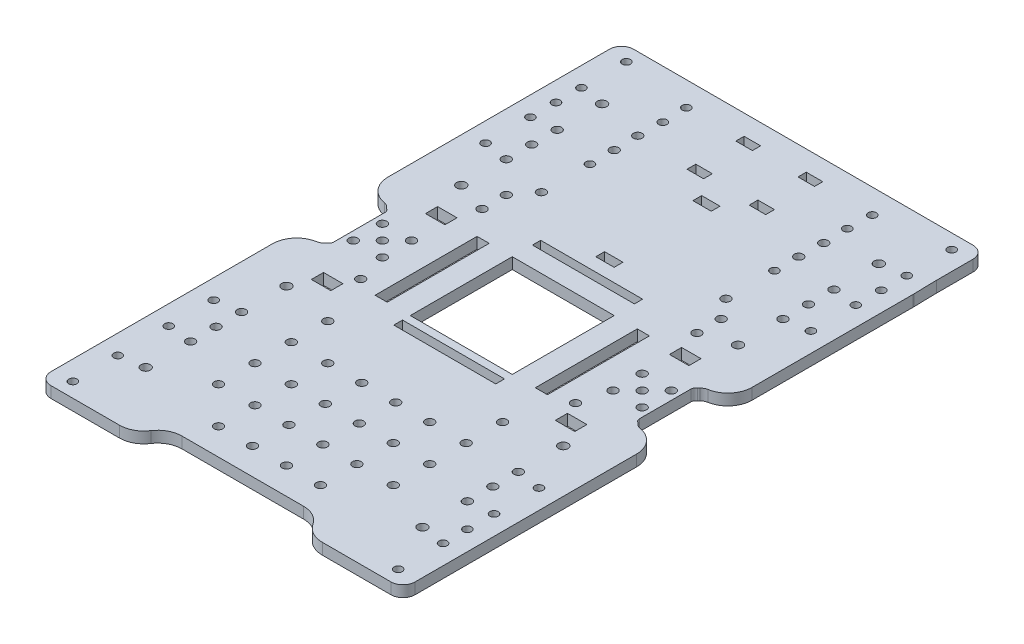
SolidWorks part; units mm, degrees
ref_plane "前视基准面" through (0, 0, 0) normal (0, 0, 1) x (1, 0, 0)
ref_plane "上视基准面" through (0, 0, 0) normal (0, 1, 0) x (1, 0, 0)
ref_plane "右视基准面" through (0, 0, 0) normal (1, 0, 0) x (0, 0, -1)
other "Configuration Table"
sketch "草图2" plane through (0, 0, 0) normal (0, 1, 0) x (1, 0, 0)
  line L0 (-65, 0) -> (65, 0) construction
  line L1 (-65, 100) -> (65, 100)
  line L2 (-65, 100) -> (-65, -100)
  line L3 (-65, -100) -> (65, -100)
  line L4 (65, 100) -> (65, -100)
  line L5 (-65, 100) -> (65, -100) construction
  line L6 (-65, -100) -> (65, 100) construction
  line L7 (65, 0) -> (63, 0) construction
  line L8 (63, 0) -> (59.5, 0) construction
  line L9 (59.5, 0) -> (47.5, 0) construction
  line L10 (47.5, 0) -> (53.5, 0) construction
  line L11 (53.5, 0) -> (53.5, 6) construction
  line L12 (53.5, 6) -> (53.5, -6) construction
  line L13 (53.5, -6) -> (47.5, -6) construction
  line L14 (47.5, -6) -> (47.5, 6) construction
  line L15 (47.5, 6) -> (59.5, 6) construction
  line L16 (59.5, 6) -> (59.5, -6) construction
  line L17 (-65, 0) -> (-63, 0) construction
  line L18 (-63, 0) -> (-59.5, 0) construction
  line L19 (-59.5, 0) -> (-47.5, 0) construction
  line L20 (-47.5, 0) -> (-53.5, 0) construction
  line L21 (-53.5, 0) -> (-53.5, 6) construction
  line L22 (-53.5, 6) -> (-53.5, -6) construction
  line L23 (-53.5, -6) -> (-59.5, -6) construction
  line L24 (-59.5, -6) -> (-59.5, 6) construction
  line L25 (-59.5, 6) -> (-47.5, 6) construction
  line L26 (-47.5, 6) -> (-47.5, -6) construction
  circle A0 centre (-59.5, 6) radius 1.8
  circle A1 centre (-47.5, 6) radius 1.8
  circle A2 centre (-59.5, -6) radius 1.8
  circle A3 centre (-47.5, -6) radius 1.8
  circle A4 centre (-53.5, 0) radius 1.8
  circle A5 centre (53.5, 0) radius 1.8
  circle A6 centre (59.5, 6) radius 1.8
  circle A7 centre (59.5, -6) radius 1.8
  circle A8 centre (47.5, -6) radius 1.8
  circle A9 centre (47.5, 6) radius 1.8
  point P0 (0, 0)
  dimension "D13" = 3.6
  dimension "D14" = 3.6
  dimension "D15" = 3.6
  dimension "D16" = 3.6
  dimension "D17" = 3.6
  dimension "D18" = 3.6
  dimension "D19" = 3.6
  dimension "D20" = 3.6
  dimension "D21" = 3.6
  dimension "D22" = 3.6
  dimension "D1" = 200
  dimension "D2" = 130
  dimension "D3" = 2
  dimension "D4" = 3.5
  dimension "D5" = 12
  dimension "D6" = 6
  dimension "D7" = 12
  dimension "D8" = 2
  dimension "D9" = 3.5
  dimension "D10" = 12
  dimension "D11" = 6
  dimension "D12" = 12
extrude "凸台-拉伸1" add sketch "草图2" along normal blind 4.6
fillet "圆角1" radius 5 4 edges at (-65, 2.3, -100) (65, 2.3, -100) (-65, 2.3, 100) (65, 2.3, 100)
sketch "草图3" plane through (0, 4.6, 0) normal (0, 1, 0) x (1, 0, 0)
  line L0 (-65, 0) -> (65, 0) construction
  line L1 (-65, 95) -> (-65, -95) construction
  line L2 (65, -95) -> (65, 95) construction
  line L4 (-63, 12) -> (-67, 12)
  line L5 (-63, 12) -> (-63, -12)
  line L6 (-63, -12) -> (-67, -12)
  line L7 (-67, 12) -> (-67, -12)
  line L8 (-63, 12) -> (-67, -12) construction
  line L9 (-63, -12) -> (-67, 12) construction
  line L10 (63, 12) -> (67, 12)
  line L11 (63, 12) -> (63, -12)
  line L12 (63, -12) -> (67, -12)
  line L13 (67, 12) -> (67, -12)
  line L14 (63, 12) -> (67, -12) construction
  line L15 (63, -12) -> (67, 12) construction
  dimension "D1" = 24
  dimension "D2" = 4
  dimension "D3" = 24
  dimension "D4" = 4
extrude "切除-拉伸1" cut sketch "草图3" against normal blind 4.6
fillet "圆角2" radius 2 4 edges at (65, 2.3, 12) (65, 2.3, -12) (-65, 2.3, 12) (-65, 2.3, -12)
fillet "圆角3" radius 2 4 edges at (-63, 2.3, 12) (-63, 2.3, -12) (63, 2.3, 12) (63, 2.3, -12)
sketch "草图4" plane through (0, 0, 0) normal (0, 1, 0) x (1, 0, 0)
  line L0 (65, 14) -> (57, 14) construction
  line L1 (57, 14) -> (57, 120) construction
  line L2 (65, -14) -> (57, -14) construction
  line L3 (65, -95) -> (65, -14) construction
  line L4 (57, -14) -> (57, -94) construction
  line L5 (57, -94) -> (57, -65) construction
  line L6 (57, -65) -> (57, -54) construction
  line L7 (-65, -94) -> (-57, -94) construction
  line L8 (-65, -14) -> (-65, -95) construction
  line L9 (-57, -94) -> (-57, -65) construction
  line L10 (-57, -65) -> (-57, -54.5) construction
  line L11 (-57, -54.5) -> (-57, -65) construction
  line L12 (-57, -65) -> (-57, -36) construction
  line L13 (57, -65) -> (57, -36) construction
  line L14 (57, 14) -> (57, 36) construction
  line L15 (57, 36) -> (57, 65) construction
  line L16 (57, 65) -> (57, 75.5) construction
  line L17 (57, 75.5) -> (57, 54.5) construction
  line L18 (57, 65) -> (57, 94) construction
  line L19 (-65, 14) -> (-57, 14) construction
  line L20 (-57, 14) -> (-57, 36) construction
  line L21 (-57, 36) -> (-57, 54.5) construction
  line L22 (-57, 54.5) -> (-57, 65) construction
  line L23 (-57, 65) -> (-57, 75.5) construction
  line L24 (-57, 75.5) -> (-57, 94) construction
  line L25 (-57, -65) -> (-57, -75.5) construction
  line L26 (-57, -75.5) -> (57, -75.5) construction
  line L27 (57, -65) -> (57, -54.5) construction
  arc A0 (65, -14) -> (64, -12.2679) centre (63, -14) ccw construction
  circle A1 centre (57, 65) radius 1.8
  circle A2 centre (57, 75.5) radius 1.8
  circle A3 centre (57, 54.5) radius 1.8
  circle A4 centre (57, 94) radius 1.95
  circle A5 centre (57, 36) radius 1.95
  circle A6 centre (-57, 94) radius 1.95
  circle A7 centre (-57, 75.5) radius 1.8
  circle A8 centre (-57, 65) radius 1.8
  circle A9 centre (-57, 54.5) radius 1.8
  circle A10 centre (-57, 36) radius 1.95
  circle A11 centre (-57, -36) radius 1.95
  circle A12 centre (-57, -65) radius 1.8
  circle A13 centre (-57, -54.5) radius 1.8
  circle A14 centre (-57, -75.5) radius 1.8
  circle A15 centre (-57, -94) radius 1.95
  circle A16 centre (57, -65) radius 1.8
  circle A18 centre (57, -75.5) radius 1.8
  circle A19 centre (57, -54.5) radius 1.8
  circle A20 centre (57, -36) radius 1.95
  circle A21 centre (57, -94) radius 1.95
  dimension "D15" = 3.6
  dimension "D16" = 3.6
  dimension "D17" = 3.6
  dimension "D18" = 3.9
  dimension "D19" = 3.9
  dimension "D20" = 3.9
  dimension "D21" = 3.6
  dimension "D22" = 3.6
  dimension "D23" = 3.6
  dimension "D24" = 3.9
  dimension "D25" = 3.9
  dimension "D26" = 3.6
  dimension "D27" = 3.6
  dimension "D29" = 3.6
  dimension "D30" = 3.9
  dimension "D31" = 3.6
  dimension "D32" = 10.5
  dimension "D33" = 3.6
  dimension "D34" = 3.6
  dimension "D35" = 3.9
  dimension "D36" = 3.9
  dimension "D1" = 8
  dimension "D2" = 106
  dimension "D3" = 8
  dimension "D4" = 80
  dimension "D5" = 29
  dimension "D6" = 11
  dimension "D7" = 8
  dimension "D8" = 29
  dimension "D9" = 22
  dimension "D10" = 29
  dimension "D11" = 10.5
  dimension "D12" = 21
  dimension "D13" = 29
  dimension "D14" = 8
  dimension "D28" = 10.5
extrude "切除-拉伸2" cut sketch "草图4" along normal blind 4.6
sketch "草图5" plane through (0, 4.6, 0) normal (0, 1, 0) x (1, 0, 0)
  line L0 (0, 100) -> (38.3, 100) construction
  line L1 (60, 100) -> (-60, 100) construction
  line L2 (38.3, 100) -> (-38.3, 100) construction
  line L3 (-38.3, 100) -> (-38.3, 90) construction
  line L4 (-38.3, 90) -> (-12.8, 90) construction
  line L5 (38.3, 100) -> (38.3, 90) construction
  line L6 (38.3, 90) -> (12.8, 90) construction
  line L7 (0, 21) -> (0, 31) construction
  line L8 (-16.2, 91.8) -> (-9.4, 91.8)
  line L9 (-16.2, 91.8) -> (-16.2, 88.2)
  line L10 (-16.2, 88.2) -> (-9.4, 88.2)
  line L11 (-9.4, 91.8) -> (-9.4, 88.2)
  line L12 (-16.2, 91.8) -> (-9.4, 88.2) construction
  line L13 (-16.2, 88.2) -> (-9.4, 91.8) construction
  line L14 (9.4, 91.8) -> (16.2, 91.8)
  line L15 (9.4, 91.8) -> (9.4, 88.2)
  line L16 (9.4, 88.2) -> (16.2, 88.2)
  line L17 (16.2, 91.8) -> (16.2, 88.2)
  line L18 (9.4, 91.8) -> (16.2, 88.2) construction
  line L19 (9.4, 88.2) -> (16.2, 91.8) construction
  line L20 (-21, 21) -> (21, 21)
  line L21 (-21, 21) -> (-21, -21)
  line L22 (-21, -21) -> (21, -21)
  line L23 (21, 21) -> (21, -21)
  line L24 (-21, 21) -> (21, -21) construction
  line L25 (-21, -21) -> (21, 21) construction
  line L26 (0, 31) -> (0, -21) construction
  line L27 (0, -21) -> (0, -31) construction
  line L28 (-60, -100) -> (60, -100) construction
  line L29 (-21, 32.7) -> (21, 32.7)
  line L30 (-21, 32.7) -> (-21, 29.3)
  line L31 (-21, 29.3) -> (21, 29.3)
  line L32 (21, 32.7) -> (21, 29.3)
  line L33 (-21, 32.7) -> (21, 29.3) construction
  line L34 (-21, 29.3) -> (21, 32.7) construction
  line L35 (-21, -29.3) -> (21, -29.3)
  line L36 (-21, -29.3) -> (-21, -32.7)
  line L37 (-21, -32.7) -> (21, -32.7)
  line L38 (21, -29.3) -> (21, -32.7)
  line L39 (-21, -29.3) -> (21, -32.7) construction
  line L40 (-21, -32.7) -> (21, -29.3) construction
  line L41 (-35, -91) -> (35, -91)
  line L42 (-35, -91) -> (-35, -109)
  line L43 (-35, -109) -> (35, -109)
  line L44 (35, -91) -> (35, -109)
  line L45 (-35, -91) -> (35, -109) construction
  line L46 (-35, -109) -> (35, -91) construction
  circle A0 centre (38.3, 90) radius 1.8
  circle A1 centre (-38.3, 90) radius 1.8
  point P19 (0, 0)
  point P37 (0, -100)
  dimension "D7" = 3.6
  dimension "D8" = 3.6
  dimension "D1" = 38.3
  dimension "D2" = 76.6
  dimension "D3" = 10
  dimension "D4" = 25.5
  dimension "D5" = 10
  dimension "D6" = 25.5
  dimension "D9" = 3.6
  dimension "D10" = 6.8
  dimension "D11" = 3.6
  dimension "D12" = 6.8
  dimension "D13" = 42
  dimension "D14" = 10
  dimension "D15" = 10
  dimension "D16" = 3.4
  dimension "D17" = 42
  dimension "D18" = 3.4
  dimension "D19" = 42
  dimension "D20" = 18
  dimension "D21" = 70
extrude "切除-拉伸3" cut sketch "草图5" against normal blind 4.6
fillet "圆角4" radius 10 2 edges at (-35, 2.3, 100) (35, 2.3, 100)
fillet "圆角5" radius 10 2 edges at (-35, 2.3, 91) (35, 2.3, 91)
sketch "草图6" plane through (0, 4.6, 0) normal (0, 1, 0) x (1, 0, 0)
  line L0 (0, -91) -> (0, -85) construction
  line L1 (28.2466, -91) -> (-28.2466, -91) construction
  line L2 (0, -85) -> (-7, -85) construction
  line L3 (-7, -85) -> (7, -85) construction
  line L4 (7, -85) -> (21, -85) construction
  line L5 (21, -85) -> (21, -70) construction
  line L6 (21, -70) -> (21, -55) construction
  line L7 (21, -55) -> (7, -55) construction
  line L8 (7, -55) -> (-7, -55) construction
  line L9 (-7, -55) -> (-21, -55) construction
  line L10 (-21, -55) -> (-35, -55) construction
  line L11 (-35, -55) -> (-35, -70) construction
  line L12 (-35, -70) -> (-35, -85) construction
  line L13 (-35, -85) -> (-21, -85) construction
  line L14 (21, -85) -> (35, -85) construction
  line L15 (35, -85) -> (35, -70) construction
  line L16 (35, -70) -> (35, -55) construction
  line L17 (35, -55) -> (35, -40) construction
  line L18 (35, -40) -> (21, -40) construction
  line L19 (21, -40) -> (7, -40) construction
  line L20 (7, -40) -> (-7, -40) construction
  line L21 (-7, -40) -> (-21, -40) construction
  line L22 (-21, -40) -> (-35, -40) construction
  line L23 (-35, -40) -> (-35, -70) construction
  line L24 (-35, -70) -> (-21, -70) construction
  line L25 (-21, -70) -> (-7, -70) construction
  line L26 (-7, -70) -> (7, -70) construction
  line L27 (21, -70) -> (36, -70) construction
  line L28 (36, -70) -> (36, -55) construction
  line L29 (36, -55) -> (36, -40) construction
  line L30 (-21, -70) -> (-36, -70) construction
  line L31 (-36, -70) -> (-36, -55) construction
  line L32 (-36, -55) -> (-36, -40) construction
  circle A0 centre (-7, -85) radius 1.8
  circle A1 centre (-21, -85) radius 1.8
  circle A2 centre (7, -85) radius 1.8
  circle A3 centre (21, -85) radius 1.8
  circle A4 centre (21, -70) radius 1.8
  circle A5 centre (7, -70) radius 1.8
  circle A6 centre (-7, -70) radius 1.8
  circle A7 centre (-21, -70) radius 1.8
  circle A8 centre (-21, -55) radius 1.8
  circle A9 centre (-7, -55) radius 1.8
  circle A10 centre (7, -55) radius 1.8
  circle A11 centre (21, -55) radius 1.8
  circle A12 centre (36, -70) radius 1.8
  circle A13 centre (36, -55) radius 1.8
  circle A14 centre (36, -40) radius 1.8
  circle A15 centre (-36, -40) radius 1.8
  circle A16 centre (-36, -55) radius 1.8
  circle A17 centre (-36, -70) radius 1.8
  dimension "D15" = 3.6
  dimension "D16" = 3.6
  dimension "D17" = 3.6
  dimension "D18" = 3.6
  dimension "D19" = 3.6
  dimension "D20" = 3.6
  dimension "D21" = 3.6
  dimension "D22" = 3.6
  dimension "D23" = 3.6
  dimension "D24" = 3.6
  dimension "D25" = 3.6
  dimension "D26" = 3.6
  dimension "D27" = 15
  dimension "D33" = 3.6
  dimension "D34" = 3.6
  dimension "D35" = 3.6
  dimension "D36" = 3.6
  dimension "D37" = 3.6
  dimension "D38" = 3.6
  dimension "D1" = 6
  dimension "D2" = 7
  dimension "D3" = 14
  dimension "D4" = 14
  dimension "D5" = 15
  dimension "D6" = 15
  dimension "D7" = 14
  dimension "D8" = 14
  dimension "D9" = 14
  dimension "D10" = 14
  dimension "D11" = 15
  dimension "D12" = 14
  dimension "D13" = 14
  dimension "D14" = 15
  dimension "D28" = 15
  dimension "D29" = 15
  dimension "D30" = 15
  dimension "D31" = 15
  dimension "D32" = 15
extrude "切除-拉伸4" cut sketch "草图6" against normal blind 4.6
sketch "草图7" plane through (0, 4.6, 0) normal (0, 1, 0) x (1, 0, 0)
  line L0 (0, 100) -> (38, 100) construction
  line L1 (60, 100) -> (-60, 100) construction
  line L2 (38, 100) -> (-38, 100) construction
  line L3 (-38, 100) -> (-38, 80) construction
  line L4 (-38, 80) -> (-38, 50) construction
  line L5 (-38, 50) -> (38, 50) construction
  line L6 (38, 50) -> (38, 80) construction
  circle A0 centre (-38, 80) radius 1.8
  circle A1 centre (38, 80) radius 1.8
  circle A2 centre (38, 50) radius 1.8
  circle A3 centre (-38, 50) radius 1.8
  dimension "D7" = 3.6
  dimension "D8" = 3.6
  dimension "D9" = 3.6
  dimension "D10" = 3.6
  dimension "D1" = 38
  dimension "D2" = 76
  dimension "D3" = 20
  dimension "D4" = 30
  dimension "D5" = 76
  dimension "D6" = 30
extrude "切除-拉伸5" cut sketch "草图7" against normal blind 4.6
sketch "草图8" plane through (0, 4.6, 0) normal (0, 1, 0) x (1, 0, 0)
  line L0 (-38, 80) -> (38, 50) construction
  line L1 (38, 50) -> (0, 65) construction
  line L2 (0, 65) -> (-35, 65) construction
  line L3 (-35, 65) -> (35, 65) construction
  line L4 (35, 65) -> (0, 65) construction
  line L5 (0, 65) -> (0, 80) construction
  line L6 (0, 80) -> (0, 40) construction
  line L8 (-3.7805, 81.7985) -> (3.7805, 81.7985)
  line L9 (-3.7805, 81.7985) -> (-3.7805, 78.2015)
  line L10 (-3.7805, 78.2015) -> (3.7805, 78.2015)
  line L11 (3.7805, 81.7985) -> (3.7805, 78.2015)
  line L12 (-3.7805, 81.7985) -> (3.7805, 78.2015) construction
  line L13 (-3.7805, 78.2015) -> (3.7805, 81.7985) construction
  line L14 (-3.7805, 38.1892) -> (3.7805, 38.1892)
  line L15 (-3.7805, 38.1892) -> (-3.7805, 41.8108)
  line L16 (-3.7805, 41.8108) -> (3.7805, 41.8108)
  line L17 (3.7805, 38.1892) -> (3.7805, 41.8108)
  line L18 (-3.7805, 38.1892) -> (3.7805, 41.8108) construction
  line L19 (-3.7805, 41.8108) -> (3.7805, 38.1892) construction
  line L20 (33.2, 68.4) -> (36.8, 68.4)
  line L21 (33.2, 68.4) -> (33.2, 61.6)
  line L22 (33.2, 61.6) -> (36.8, 61.6)
  line L23 (36.8, 68.4) -> (36.8, 61.6)
  line L24 (33.2, 68.4) -> (36.8, 61.6) construction
  line L25 (33.2, 61.6) -> (36.8, 68.4) construction
  line L26 (-36.8, 68.4) -> (-33.2, 68.4)
  line L27 (-36.8, 68.4) -> (-36.8, 61.6)
  line L28 (-36.8, 61.6) -> (-33.2, 61.6)
  line L29 (-33.2, 68.4) -> (-33.2, 61.6)
  line L30 (-36.8, 68.4) -> (-33.2, 61.6) construction
  line L31 (-36.8, 61.6) -> (-33.2, 68.4) construction
  dimension "D1" = 35
  dimension "D2" = 70
  dimension "D3" = 40
  dimension "D4" = 6.8
  dimension "D5" = 3.6
  dimension "D6" = 6.8
  dimension "D7" = 3.6
extrude "切除-拉伸6" cut sketch "草图8" against normal blind 4.6
sketch "草图10" plane through (0, 4.6, 0) normal (0, 1, 0) x (1, 0, 0)
  line L0 (0, 0) -> (44.25, 0) construction
  line L1 (44.25, 0) -> (-44.25, 0) construction
  line L2 (36, -38.2) -> (73.5514, -38.2) construction
  line L3 (73.5514, -38.2) -> (-76.1567, -38.2) construction
  line L4 (44.25, 0) -> (44.25, -38.2) construction
  line L5 (44.25, -38.2) -> (44.25, -18.2) construction
  line L6 (-44.25, 0) -> (-44.25, -38.2) construction
  line L7 (-44.25, -38.2) -> (-44.25, -18.1899) construction
  line L8 (-44.25, -18.1899) -> (-43.1477, 41.8) construction
  line L9 (-43.1477, 41.8) -> (44.25, 41.8) construction
  line L10 (0, 38.1892) -> (-44.25, 38.1892) construction
  line L11 (-3.7805, 38.1892) -> (3.7805, 38.1892) construction
  line L12 (-44.25, 38.1892) -> (44.25, 38.1892) construction
  line L13 (-44.25, -18.1899) -> (-44.25, 41.8101) construction
  line L14 (44.25, -18.2) -> (44.25, 41.8) construction
  line L15 (44.25, -18.2) -> (44.25, -8.2) construction
  line L16 (-44.25, -18.1899) -> (-44.25, -8.1899) construction
  line L17 (-44.25, -18.1899) -> (-44.25, 31.8101) construction
  line L18 (-44.25, 31.8101) -> (44.25, 31.8101) construction
  circle A0 centre (36, -40) radius 1.8 construction
  circle A1 centre (44.25, 41.8) radius 1.8
  circle A2 centre (-44.25, 41.8101) radius 1.8
  circle A3 centre (-44.25, -18.1899) radius 1.8
  circle A4 centre (44.25, -18.2) radius 1.8
  circle A5 centre (-44.25, 31.8101) radius 1.8
  circle A6 centre (44.25, 31.8101) radius 1.8
  dimension "D9" = 3.6
  dimension "D10" = 3.6
  dimension "D11" = 3.6
  dimension "D12" = 3.6
  dimension "D16" = 3.6
  dimension "D17" = 3.6
  dimension "D1" = 44.25
  dimension "D2" = 88.5
  dimension "D3" = 20
  dimension "D4" = 60
  dimension "D5" = 44.25
  dimension "D6" = 88.5
  dimension "D7" = 60
  dimension "D8" = 60
  dimension "D13" = 10
  dimension "D14" = 10
  dimension "D15" = 50
extrude "切除-拉伸8" cut sketch "草图10" against normal blind 4.6
sketch "草图9" plane through (0, 4.6, 0) normal (0, 1, 0) x (1, 0, 0)
  line L0 (21, 0) -> (33, 0) construction
  line L1 (21, -21) -> (21, 21) construction
  line L2 (-21, 0) -> (-33, 0) construction
  line L3 (-21, 21) -> (-21, -21) construction
  line L4 (35.5, -21) -> (65, -21) construction
  line L9 (30.5, 21) -> (35.5, -21) construction
  line L10 (30.5, -21) -> (35.5, 21) construction
  line L15 (-35.5, 21) -> (-30.5, -21) construction
  line L16 (-35.5, -21) -> (-30.5, 21) construction
  line L17 (65, -95) -> (65, -14) construction
  line L18 (-35.5, -21) -> (-65, -21) construction
  line L23 (46.25, -18.5) -> (54.25, -23.5) construction
  line L24 (46.25, -23.5) -> (54.25, -18.5) construction
  line L25 (-65, -14) -> (-65, -95) construction
  line L26 (-35.5, 21) -> (-65, 21) construction
  line L31 (-54.25, -18.5) -> (-46.25, -23.5) construction
  line L32 (-54.25, -23.5) -> (-46.25, -18.5) construction
  line L33 (-65, 95) -> (-65, 14) construction
  line L34 (35.5, 21) -> (65, 21) construction
  line L35 (-54.25, 23.5) -> (-46.25, 23.5)
  line L36 (-54.25, 23.5) -> (-54.25, 18.5)
  line L37 (-54.25, 18.5) -> (-46.25, 18.5)
  line L38 (-46.25, 23.5) -> (-46.25, 18.5)
  line L39 (-54.25, 23.5) -> (-46.25, 18.5) construction
  line L40 (-54.25, 18.5) -> (-46.25, 23.5) construction
  line L41 (65, 14) -> (65, 95) construction
  line L42 (50.25, -21) -> (50.25, -31) construction
  line L43 (46.25, 23.5) -> (54.25, 23.5)
  line L44 (46.25, 23.5) -> (46.25, 18.5)
  line L45 (46.25, 18.5) -> (54.25, 18.5)
  line L46 (54.25, 23.5) -> (54.25, 18.5)
  line L47 (46.25, 23.5) -> (54.25, 18.5) construction
  line L48 (46.25, 18.5) -> (54.25, 23.5) construction
  line L49 (50.25, -31) -> (50.25, -26) construction
  line L50 (50.25, -26) -> (-50.25, -26) construction
  line L52 (-54.25, -23.5) -> (-46.25, -23.5)
  line L53 (-54.25, -23.5) -> (-54.25, -28.5)
  line L54 (-54.25, -28.5) -> (-46.25, -28.5)
  line L55 (-46.25, -23.5) -> (-46.25, -28.5)
  line L56 (-54.25, -23.5) -> (-46.25, -28.5) construction
  line L57 (-54.25, -28.5) -> (-46.25, -23.5) construction
  line L58 (46.25, -23.5) -> (54.25, -23.5)
  line L59 (46.25, -23.5) -> (46.25, -28.5)
  line L60 (46.25, -28.5) -> (54.25, -28.5)
  line L61 (54.25, -23.5) -> (54.25, -28.5)
  line L62 (46.25, -23.5) -> (54.25, -28.5) construction
  line L63 (46.25, -28.5) -> (54.25, -23.5) construction
  line L64 (30.5, 21) -> (35.5, 21)
  line L65 (30.5, 21) -> (30.5, -21)
  line L66 (30.5, -21) -> (35.5, -21)
  line L67 (35.5, 21) -> (35.5, -21)
  line L68 (30.5, 21) -> (35.5, -21) construction
  line L69 (30.5, -21) -> (35.5, 21) construction
  line L70 (-35.5, 21) -> (-30.5, 21)
  line L71 (-35.5, 21) -> (-35.5, -21)
  line L72 (-35.5, -21) -> (-30.5, -21)
  line L73 (-30.5, 21) -> (-30.5, -21)
  line L74 (-35.5, 21) -> (-30.5, -21) construction
  line L75 (-35.5, -21) -> (-30.5, 21) construction
  point P17 (50.25, -21)
  point P25 (-50.25, -21)
  point P33 (-50.25, 21)
  point P41 (50.25, 21)
  dimension "D1" = 12
  dimension "D2" = 12
  dimension "D3" = 42
  dimension "D4" = 5
  dimension "D5" = 42
  dimension "D6" = 5
  dimension "D7" = 5
  dimension "D8" = 8
  dimension "D9" = 5
  dimension "D10" = 8
  dimension "D11" = 5
  dimension "D12" = 8
  dimension "D13" = 5
  dimension "D14" = 8
  dimension "D15" = 10
  dimension "D16" = 5
  dimension "D17" = 8
  dimension "D18" = 5
  dimension "D19" = 8
extrude "切除-拉伸9" cut sketch "草图9" against normal blind 4.6
sketch "草图12" plane through (0, 0, 0) normal (0, -1, 0) x (1, 0, 0)
  line L0 (-46.25, 28.5) -> (-46.25, 23.5) construction
  line L1 (-65, 100) -> (-46.25, 100)
  line L2 (-65, 100) -> (-65, 28.5)
  line L3 (-65, 28.5) -> (-46.25, 28.5)
  line L4 (-46.25, 100) -> (-46.25, 28.5)
  line L5 (-54.25, 28.5) -> (-46.25, 28.5) construction
  line L6 (65, 95) -> (65, 100.0021) construction
  line L7 (-60, -100) -> (-65, -100) construction
  line L8 (65, 100.0021) -> (46.25, 100.0021)
  line L9 (65, 100.0021) -> (65, 28.5)
  line L10 (65, 28.5) -> (46.25, 28.5)
  line L11 (46.25, 100.0021) -> (46.25, 28.5)
  line L12 (-46.25, -23.5) -> (-54.25, -23.5) construction
  line L13 (-65, -100) -> (-50.25, -100)
  line L14 (-65, -100) -> (-65, -23.5)
  line L15 (-65, -23.5) -> (-50.25, -23.5)
  line L16 (-50.25, -100) -> (-50.25, -23.5)
  line L17 (54.25, -23.5) -> (46.25, -23.5) construction
  line L18 (65, -99.9979) -> (50.25, -99.9979)
  line L19 (65, -99.9979) -> (65, -23.5)
  line L20 (65, -23.5) -> (50.25, -23.5)
  line L21 (50.25, -99.9979) -> (50.25, -23.5)
  line L22 (-50.25, -55.9334) -> (50.25, -55.9334) construction
  line L23 (50.25, -55.9334) -> (50.25, -72.845) construction
  line L24 (50.25, -72.845) -> (-50.25, -72.845) construction
  line L25 (-21, 85) -> (-21, 70) construction
  line L26 (-21, 70) -> (-21, 77.5) construction
  line L27 (-21, 77.5) -> (-46.25, 77.5) construction
  line L28 (-46.25, 77.5) -> (46.25, 77.5) construction
  line L29 (46.25, 77.5) -> (0, 77.5) construction
  line L30 (0, 77.5) -> (0, 62.5) construction
  line L31 (0, 62.5) -> (0, 47.5) construction
  line L32 (0, 77.5) -> (0, 92.5) construction
  line L33 (-28.2466, 91) -> (-46.25, 91) construction
  line L34 (-46.25, 91) -> (46.25, 91) construction
  line L35 (-21, 32.7) -> (-46.25, 32.7) construction
  line L36 (-46.25, 79.5003) -> (46.25, 79.5003)
  line L37 (-46.25, 79.5003) -> (-46.25, 75.4997)
  line L38 (-46.25, 75.4997) -> (46.25, 75.4997)
  line L39 (46.25, 79.5003) -> (46.25, 75.4997)
  line L40 (-46.25, 79.5003) -> (46.25, 75.4997) construction
  line L41 (-46.25, 75.4997) -> (46.25, 79.5003) construction
  line L42 (-46.25, 64.5) -> (46.25, 64.5)
  line L43 (-46.25, 64.5) -> (-46.25, 60.5)
  line L44 (-46.25, 60.5) -> (46.25, 60.5)
  line L45 (46.25, 64.5) -> (46.25, 60.5)
  line L46 (-46.25, 64.5) -> (46.25, 60.5) construction
  line L47 (-46.25, 60.5) -> (46.25, 64.5) construction
  line L48 (-46.25, 49.5) -> (46.25, 49.5)
  line L49 (-46.25, 49.5) -> (-46.25, 45.5)
  line L50 (-46.25, 45.5) -> (46.25, 45.5)
  line L51 (46.25, 49.5) -> (46.25, 45.5)
  line L52 (-46.25, 49.5) -> (46.25, 45.5) construction
  line L53 (-46.25, 45.5) -> (46.25, 49.5) construction
  line L54 (-46.25, 91) -> (46.25, 91)
  line L55 (-46.25, 91) -> (-46.25, 89)
  line L56 (-46.25, 89) -> (46.25, 89)
  line L57 (46.25, 91) -> (46.25, 89)
  line L58 (-46.25, 32.7) -> (46.25, 32.7) construction
  line L59 (0, -55.9334) -> (0, -57.8166) construction
  line L60 (-46.25, 32.7) -> (46.25, 32.7)
  line L61 (-46.25, 32.7) -> (-46.25, 34.7)
  line L62 (-46.25, 34.7) -> (46.25, 34.7)
  line L63 (46.25, 32.7) -> (46.25, 34.7)
  line L64 (-38, -81.8) -> (-38, -88.2252) construction
  line L65 (-50.25, -54.875) -> (50.25, -54.875)
  line L66 (-50.25, -54.875) -> (-50.25, -58.875)
  line L67 (-50.25, -58.875) -> (50.25, -58.875)
  line L68 (50.25, -54.875) -> (50.25, -58.875)
  line L69 (-50.25, -54.875) -> (50.25, -58.875) construction
  line L70 (-50.25, -58.875) -> (50.25, -54.875) construction
  line L71 (-50.25, -74.845) -> (50.25, -74.845)
  line L72 (-50.25, -74.845) -> (-50.25, -70.845)
  line L73 (-50.25, -70.845) -> (50.25, -70.845)
  line L74 (50.25, -74.845) -> (50.25, -70.845)
  line L75 (-50.25, -74.845) -> (50.25, -70.845) construction
  line L76 (-50.25, -70.845) -> (50.25, -74.845) construction
  line L77 (-38, -85.0126) -> (67.8048, -85.0126) construction
  line L78 (0, -81.7985) -> (0, -85.0126) construction
  line L79 (3.7805, -81.7985) -> (-3.7805, -81.7985) construction
  line L80 (0, -85.0126) -> (0, -95.8032) construction
  line L81 (-50.25, -84.0126) -> (50.25, -84.0126)
  line L82 (-50.25, -84.0126) -> (-50.25, -86.0126)
  line L83 (-50.25, -86.0126) -> (50.25, -86.0126)
  line L84 (50.25, -84.0126) -> (50.25, -86.0126)
  line L85 (-50.25, -84.0126) -> (50.25, -86.0126) construction
  line L86 (-50.25, -86.0126) -> (50.25, -84.0126) construction
  line L87 (0, -56.875) -> (0, -72.845) construction
  line L88 (-50.25, -94.3032) -> (50.25, -94.3032)
  line L89 (-50.25, -94.3032) -> (-50.25, -97.3032)
  line L90 (-50.25, -97.3032) -> (50.25, -97.3032)
  line L91 (50.25, -94.3032) -> (50.25, -97.3032)
  line L92 (-50.25, -94.3032) -> (50.25, -97.3032) construction
  line L93 (-50.25, -97.3032) -> (50.25, -94.3032) construction
  line L94 (3.7805, -80) -> (36.2, -80) construction
  line L95 (-2, -58.875) -> (2, -58.875)
  line L96 (-2, -58.875) -> (-2, -70.845)
  line L97 (-2, -70.845) -> (2, -70.845)
  line L98 (2, -58.875) -> (2, -70.845)
  line L99 (-2, -58.875) -> (2, -70.845) construction
  line L100 (-2, -70.845) -> (2, -58.875) construction
  line L101 (3.7805, -78.2015) -> (3.7805, -81.7985) construction
  line L102 (-3.7805, -80) -> (-36.2, -80) construction
  line L103 (-3.7805, -81.7985) -> (-3.7805, -78.2015) construction
  line L104 (22.8, 55) -> (34.2, 55) construction
  line L105 (17.9902, -85.155) -> (21.9902, -85.155)
  line L106 (17.9902, -85.155) -> (17.9902, -74.845)
  line L107 (17.9902, -74.845) -> (21.9902, -74.845)
  line L108 (21.9902, -85.155) -> (21.9902, -74.845)
  line L109 (17.9902, -85.155) -> (21.9902, -74.845) construction
  line L110 (17.9902, -74.845) -> (21.9902, -85.155) construction
  line L111 (-21.9902, -85.845) -> (-17.9902, -85.845)
  line L112 (-21.9902, -85.845) -> (-21.9902, -74.155)
  line L113 (-21.9902, -74.155) -> (-17.9902, -74.155)
  line L114 (-17.9902, -85.845) -> (-17.9902, -74.155)
  line L115 (-21.9902, -85.845) -> (-17.9902, -74.155) construction
  line L116 (-21.9902, -74.155) -> (-17.9902, -85.845) construction
  line L117 (-2, -84.9529) -> (2, -84.9529)
  line L118 (-2, -84.9529) -> (-2, -95.8629)
  line L119 (-2, -95.8629) -> (2, -95.8629)
  line L120 (2, -84.9529) -> (2, -95.8629)
  line L121 (-2, -84.9529) -> (2, -95.8629) construction
  line L122 (-2, -95.8629) -> (2, -84.9529) construction
  line L123 (-2, 49) -> (2, 49)
  line L124 (-2, 49) -> (-2, 91)
  line L125 (-2, 91) -> (2, 91)
  line L126 (2, 49) -> (2, 91)
  line L127 (-2, 49) -> (2, 91) construction
  line L128 (-2, 91) -> (2, 49) construction
  line L129 (-34.2, 55) -> (-22.8, 55) construction
  line L131 (26.5, 75.3) -> (30.5, 75.3)
  line L132 (26.5, 75.3) -> (26.5, 34.7)
  line L133 (26.5, 34.7) -> (30.5, 34.7)
  line L134 (30.5, 75.3) -> (30.5, 34.7)
  line L135 (26.5, 75.3) -> (30.5, 34.7) construction
  line L136 (26.5, 34.7) -> (30.5, 75.3) construction
  line L137 (-30.5, 75.3) -> (-26.5, 75.3)
  line L138 (-30.5, 75.3) -> (-30.5, 34.7)
  line L139 (-30.5, 34.7) -> (-26.5, 34.7)
  line L140 (-26.5, 75.3) -> (-26.5, 34.7)
  line L141 (-30.5, 75.3) -> (-26.5, 34.7) construction
  line L142 (-30.5, 34.7) -> (-26.5, 75.3) construction
  circle A0 centre (-57, 94) radius 1.95
  circle A1 centre (-57, 75.5) radius 1.8
  circle A2 centre (-57, 65) radius 1.8143
  circle A3 centre (-57, 54.5) radius 1.8
  circle A4 centre (-57, 36) radius 1.95
  circle A5 centre (57, 94) radius 1.95
  circle A6 centre (57, 75.5) radius 1.8
  circle A7 centre (57, 65) radius 1.8
  circle A8 centre (57, 54.5) radius 1.8
  circle A9 centre (57, 36) radius 1.95
  circle A10 centre (57, -36) radius 1.95
  circle A11 centre (57, -54.5) radius 1.8
  circle A12 centre (57, -65) radius 1.8
  circle A13 centre (57, -75.5) radius 1.8
  circle A14 centre (57, -94) radius 1.95
  circle A15 centre (-57, -94) radius 1.95
  circle A16 centre (-57, -75.5) radius 1.8
  circle A17 centre (-57, -65) radius 1.8
  circle A18 centre (-57, -54.5) radius 1.8
  circle A19 centre (-57, -36) radius 1.95
  circle A20 centre (-38, -80) radius 1.8 construction
  circle A21 centre (-38.3, -90) radius 1.8 construction
  circle A22 centre (38, -80) radius 1.8 construction
  circle A23 centre (21, 55) radius 1.8 construction
  circle A24 centre (36, 55) radius 1.8 construction
  circle A25 centre (-36, 55) radius 1.8 construction
  circle A26 centre (-21, 55) radius 1.8 construction
  point P133 (0, -56.875)
  point P138 (0, -72.845)
  point P167 (0, -64.86)
  point P183 (19.9902, -80)
  point P188 (-19.9902, -80)
  point P193 (0, -90.4079)
  point P198 (0, 70)
  point P217 (28.5, 55)
  point P222 (-28.5, 55)
  dimension "D1" = 15
  dimension "D2" = 15
  dimension "D3" = 15
  dimension "D4" = 4.0007
  dimension "D5" = 92.5
  dimension "D6" = 4
  dimension "D7" = 4
  dimension "D8" = 2
  dimension "D9" = 2
  dimension "D10" = 4
  dimension "D11" = 4
  dimension "D12" = 2
  dimension "D13" = 3
  dimension "D14" = 11.97
  dimension "D15" = 4
  dimension "D16" = 10.31
  dimension "D17" = 4
  dimension "D18" = 11.69
  dimension "D19" = 4
  dimension "D20" = 10.91
  dimension "D21" = 4
  dimension "D22" = 42
  dimension "D23" = 4
  dimension "D24" = 40.6
  dimension "D25" = 4
  dimension "D26" = 40.6
  dimension "D27" = 4
extrude "凸台-拉伸2" add sketch "草图12" along normal blind 2 contours L4 L1 L2 L3 A4 A3 A2 A1 A0 | L56 L126 L54 L124 | L126 L56 L11 L54 | L56 L124 L54 L4 | L36 L126 L56 L124 | L8 L11 L10 L9 A9 A8 A7 A6 A5 | L126 L38 L11 L36 | L38 L126 L36 L124 | L38 L124 L36 L4 | L42 L126 L38 L124 | L134 L131 L132 L42 | L140 L137 L138 L42 | L138 L42 L4 L44 | L140 L42 L138 L44 | L42 L140 L44 L124 | L44 L126 L42 L124 | L132 L42 L126 L44 | L134 L42 L132 L44 | L42 L134 L44 L11 | L134 L44 L132 L48 | L48 L134 L50 L11 | L134 L50 L132 L62 | L62 L4 L60 L11 | L134 L48 L132 L50 | L48 L140 L50 L132 L126 L123 L124 | L48 L126 L44 L124 | L123 L126 L48 L124 | L140 L44 L138 L48 | L138 L48 L4 L50 | L140 L48 L138 L50 | L140 L50 L138 L62 | L21 L18 L19 L20 A14 A13 A12 A11 A10 | L13 L16 L15 L14 A19 A18 A17 A16 A15 | L16 L67 L21 L65 | L98 L67 L96 L73 | L114 L71 L21 L73 L16 L112 L113 | L81 L108 L71 L106 | L81 L114 L71 L112 | L71 L114 L113 L112 | L117 L120 L83 L21 L81 L108 L105 L106 L114 L111 L112 L16 L118 | L111 L114 L81 L112 | L105 L108 L81 L106 | L120 L117 L118 L83 | L120 L83 L118 L88 | L88 L120 L119 L118 L16 L90 L21 | L120 L88 L118 L119
sketch "草图13" plane through (0, 0, 0) normal (0, -1, 0) x (1, 0, 0)
  line L0 (0, -41.8108) -> (0, -45.8108) construction
  line L1 (3.7805, -41.8108) -> (-3.7805, -41.8108) construction
  line L3 (-15, -45.8108) -> (15, -45.8108)
  line L4 (-15, -45.8108) -> (-15, -41.8108)
  line L5 (-15, -41.8108) -> (15, -41.8108)
  line L6 (15, -45.8108) -> (15, -41.8108)
  line L7 (-15, -45.8108) -> (15, -41.8108) construction
  line L8 (-15, -41.8108) -> (15, -45.8108) construction
  point P5 (0, -43.8108)
  dimension "D1" = 4
  dimension "D2" = 4
  dimension "D3" = 30
extrude "凸台-拉伸3" add sketch "草图13" along normal blind 2
fillet "圆角6" radius 5 12 edges at (-62.5, 0, 100) (-65, 0, -97.5) (-62.5, 0, -100) (-65, -1, -100) (65, 0, -97.499) (65, -1, -99.9979) (63.5355, 0, 98.5355) (65, 2.3, -95) (65, 0, 97.501) (-65, 0, 97.5) (-65, -1, 100) (65, -1, 100.0021)
sketch "草图14" plane through (0, 4.6, 0) normal (0, 1, 0) x (1, 0, 0)
  line L1 (21, -32.7) -> (-21, -32.7)
  line L2 (21, -32.7) -> (21, -29.3)
  line L3 (21, -29.3) -> (-21, -29.3)
  line L4 (-21, -32.7) -> (-21, -29.3)
extrude "凸台-拉伸4" add sketch "草图14" against normal up to surface (4.6 mm away) up to face at (0, 0, 1.9679)
sketch "草图15" plane through (0, 4.6, 0) normal (0, 1, 0) x (1, 0, 0)
  line L0 (0, -21) -> (0, -26) construction
  line L1 (-21, -21) -> (21, -21) construction
  line L3 (-21, -24.2) -> (21, -24.2)
  line L4 (-21, -24.2) -> (-21, -27.8)
  line L5 (-21, -27.8) -> (21, -27.8)
  line L6 (21, -24.2) -> (21, -27.8)
  line L7 (-21, -24.2) -> (21, -27.8) construction
  line L8 (-21, -27.8) -> (21, -24.2) construction
  dimension "D1" = 5
  dimension "D2" = 3.6
  dimension "D3" = 42
extrude "切除-拉伸10" cut sketch "草图15" against normal blind 10
sketch "草图16" plane through (0, 0, 0) normal (0, -1, 0) x (1, 0, 0)
  line L1 (-102.4978, 109.1095) -> (102.4978, 109.1095)
  line L2 (-102.4978, 109.1095) -> (-102.4978, -109.1095)
  line L3 (-102.4978, -109.1095) -> (102.4978, -109.1095)
  line L4 (102.4978, 109.1095) -> (102.4978, -109.1095)
  line L5 (-102.4978, 109.1095) -> (102.4978, -109.1095) construction
  line L6 (-102.4978, -109.1095) -> (102.4978, 109.1095) construction
  point P0 (0, 0)
extrude "切除-拉伸11" cut sketch "草图16" along normal up to surface (2 mm away) up to face at (0, -2, -79.4288)
sketch "草图17" plane through (0, 0, 0) normal (0, 1, 0) x (1, 0, 0)
  line L1 (-60, -100) -> (-75, -100)
  line L2 (-60, -100) -> (-60, -14)
  line L3 (-60, -14) -> (-75, -14)
  line L4 (-75, -100) -> (-75, -14)
  line L5 (60, -100) -> (75, -100)
  line L6 (60, -100) -> (60, -14)
  line L7 (60, -14) -> (75, -14)
  line L8 (75, -100) -> (75, -14)
  line L9 (-60, 100) -> (-75, 100)
  line L10 (-60, 100) -> (-60, 14)
  line L11 (-60, 14) -> (-75, 14)
  line L12 (-75, 100) -> (-75, 14)
  line L13 (60, 100) -> (75, 100)
  line L14 (60, 100) -> (60, 14)
  line L15 (60, 14) -> (75, 14)
  line L16 (75, 100) -> (75, 14)
  dimension "D1" = 86
  dimension "D2" = 15
  dimension "D3" = 86
  dimension "D4" = 15
  dimension "D5" = 86
  dimension "D6" = 15
  dimension "D7" = 86
  dimension "D8" = 15
extrude "凸台-拉伸5" add sketch "草图17" along normal up to surface (4.6 mm away) up to face at (0, 4.6, 26)
fillet "圆角7" radius 3.5 4 edges at (65, 2.3, 14) (65, 2.3, -14) (-65, 2.3, -14) (-65, 2.3, 14)
fillet "圆角8" radius 10 8 edges at (75, 2.3, -100) (-75, 2.3, -100) (-75, 2.3, -14) (-75, 2.3, 14) (-75, 2.3, 100) (75, 2.3, 100) (75, 2.3, -14) (75, 2.3, 14)
sketch "草图18" plane through (0, 4.6, 0) normal (0, 1, 0) x (1, 0, 0)
  line L0 (-57, 94) -> (-67, 94) construction
  line L1 (-57, 75.5) -> (-67, 75.5) construction
  line L2 (-67, 75.5) -> (-57, 75.5) construction
  line L3 (-57, 75.5) -> (-57, 65) construction
  line L4 (-57, 65) -> (-67, 65) construction
  line L5 (-67, 65) -> (-57, 65) construction
  line L6 (-57, 65) -> (-57, 54.5) construction
  line L7 (-57, 54.5) -> (-67, 54.5) construction
  line L8 (-67, 54.5) -> (-57, 54.5) construction
  line L9 (-57, 54.5) -> (-57, 36) construction
  line L10 (-57, 36) -> (-67, 36) construction
  line L11 (-57, -36) -> (-67, -36) construction
  line L12 (-67, -36) -> (-57, -36) construction
  line L13 (-57, -36) -> (-57, -54.5) construction
  line L14 (-57, -54.5) -> (-67, -54.5) construction
  line L15 (-67, -54.5) -> (-57, -54.5) construction
  line L16 (-57, -54.5) -> (-57, -65) construction
  line L17 (-57, -65) -> (-67, -65) construction
  line L18 (-67, -65) -> (-57, -65) construction
  line L19 (-57, -65) -> (-57, -75.5) construction
  line L20 (-57, -75.5) -> (-67, -75.5) construction
  line L21 (-67, -75.5) -> (-57, -75.5) construction
  line L22 (-57, -75.5) -> (-57, -94) construction
  line L23 (-57, -94) -> (-67, -94) construction
  line L24 (57, 94) -> (67, 94) construction
  line L25 (67, 94) -> (57, 94) construction
  line L26 (57, 94) -> (57, 75.5) construction
  line L27 (57, 75.5) -> (67, 75.5) construction
  line L28 (67, 75.5) -> (57, 75.5) construction
  line L29 (57, 75.5) -> (57, 65) construction
  line L30 (57, 65) -> (67, 65) construction
  line L31 (67, 65) -> (57, 65) construction
  line L32 (57, 65) -> (57, 54.5) construction
  line L33 (57, 54.5) -> (67, 54.5) construction
  line L34 (67, 54.5) -> (57, 54.5) construction
  line L35 (57, 54.5) -> (57, 36) construction
  line L36 (57, 36) -> (67, 36) construction
  line L37 (57, -36) -> (67, -36) construction
  line L38 (67, -36) -> (57, -36) construction
  line L39 (57, -36) -> (57, -54.5) construction
  line L40 (57, -54.5) -> (67, -54.5) construction
  line L41 (67, -54.5) -> (57, -54.5) construction
  line L42 (57, -54.5) -> (57, -65) construction
  line L43 (57, -65) -> (67, -65) construction
  line L44 (67, -65) -> (57, -65) construction
  line L45 (57, -65) -> (57, -75.5) construction
  line L46 (57, -75.5) -> (67, -75.5) construction
  line L47 (67, -75.5) -> (57, -75.5) construction
  line L48 (57, -75.5) -> (57, -94) construction
  line L49 (57, -94) -> (67, -94) construction
  circle A1 centre (67, 75.5) radius 1.7
  circle A2 centre (67, 65) radius 1.7
  circle A3 centre (67, 54.5) radius 1.7
  circle A6 centre (67, -54.5) radius 1.7
  circle A7 centre (67, -65) radius 1.7
  circle A8 centre (67, -75.5) radius 1.7
  circle A11 centre (-67, -75.5) radius 1.7
  circle A12 centre (-67, -65) radius 1.7
  circle A13 centre (-67, -54.5) radius 1.7
  circle A16 centre (-67, 54.5) radius 1.7
  circle A17 centre (-67, 65) radius 1.7
  circle A18 centre (-67, 75.5) radius 1.7
  circle A19 centre (-67, 94) radius 1.8
  circle A20 centre (67, -94) radius 1.8
  circle A21 centre (67, -36) radius 1.8
  circle A22 centre (-67, -36) radius 1.8
  circle A23 centre (-67, -94) radius 1.8
  circle A24 centre (-67, 36) radius 1.8
  circle A25 centre (67, 36) radius 1.8
  circle A26 centre (67, 94) radius 1.8
  dimension "D3" = 3.6
  dimension "D4" = 3.4
  dimension "D5" = 3.4
  dimension "D6" = 3.4
  dimension "D7" = 3.6
  dimension "D8" = 3.6
  dimension "D9" = 3.4
  dimension "D10" = 3.4
  dimension "D11" = 3.4
  dimension "D12" = 3.6
  dimension "D13" = 3.6
  dimension "D14" = 3.4
  dimension "D15" = 3.4
  dimension "D16" = 3.4
  dimension "D17" = 3.6
  dimension "D18" = 3.6
  dimension "D19" = 3.4
  dimension "D20" = 3.4
  dimension "D21" = 3.4
  dimension "D22" = 3.6
  dimension "D1" = 10
  dimension "D2" = 10
extrude "切除-拉伸12" cut sketch "草图18" against normal blind 10
sketch "草图20" plane through (0, 4.6, 0) normal (0, 1, 0) x (1, 0, 0)
  line L0 (65, 100) -> (84.5699, 100) construction
  line L1 (-65, 100) -> (-97.4695, 100) construction
  line L2 (-75, 90) -> (-75, 100)
  line L3 (-75, 100) -> (-75, 120)
  line L4 (75, 90) -> (74.785, 100)
  line L5 (74.785, 100) -> (74.785, 120)
  line L6 (74.785, 120) -> (-75, 120)
  line L7 (-65, -100) -> (-88.3845, -100) construction
  line L8 (-88.3845, -100) -> (86.7466, -100) construction
  line L9 (-75, -90) -> (-75, -100)
  line L10 (-75, -100) -> (-75, -120)
  line L11 (75, -90) -> (75, -100)
  line L12 (75, -100) -> (75, -120)
  line L13 (-75, -120) -> (-35, -120)
  line L14 (-21, -70) -> (-21, -85) construction
  line L15 (-21, -85) -> (-21, -100) construction
  line L16 (-21, -100) -> (-7, -100) construction
  line L17 (-7, -100) -> (7, -100) construction
  line L18 (7, -100) -> (21, -100) construction
  line L19 (75, -120) -> (35, -120)
  line L20 (75, -100) -> (21, -100) construction
  line L21 (35, -120) -> (35, -111)
  line L22 (35, -111) -> (-35, -111)
  line L23 (-35, -111) -> (-35, -120)
  line L24 (75, -90) -> (69.1976, -96.5941)
  line L25 (69.1976, -96.5941) -> (44.9201, -96.5941)
  line L26 (44.9201, -96.5941) -> (31.6017, -88.9836)
  line L27 (31.6017, -88.9836) -> (-48.6129, -88.9836)
  line L28 (-48.6129, -88.9836) -> (-52.2659, -97.6595)
  line L29 (-52.2659, -97.6595) -> (-69.4686, -96.5941)
  line L30 (-69.4686, -96.5941) -> (-75, -90)
  line L31 (-75, 90) -> (-66.3461, 97.2593)
  line L32 (-66.3461, 97.2593) -> (60.83, 97.2593)
  line L33 (60.83, 97.2593) -> (69.1976, 97.2593)
  line L34 (69.1976, 97.2593) -> (75, 90)
  dimension "D1" = 20
  dimension "D2" = 20
  dimension "D3" = 20
  dimension "D4" = 20
  dimension "D5" = 40
  dimension "D6" = 15
  dimension "D7" = 14
  dimension "D8" = 14
  dimension "D9" = 14
  dimension "D10" = 40
  dimension "D11" = 9
extrude "凸台-拉伸6" add sketch "草图20" against normal up to surface (4.6 mm away) up to face at (-67, 0, 66.7)
sketch "草图21" plane through (0, 4.6, 0) normal (0, 1, 0) x (1, 0, 0)
  line L0 (38.3, 90) -> (38.3, 110) construction
  line L1 (-38.3, 90) -> (-38.3, 110) construction
  line L2 (-16.2, 90) -> (-9.4, 90) construction
  line L3 (-16.2, 91.8) -> (-16.2, 88.2) construction
  line L4 (-9.4, 88.2) -> (-9.4, 91.8) construction
  line L5 (-9.4, 90) -> (-12.8, 90) construction
  line L6 (-12.8, 90) -> (-12.8, 110) construction
  line L7 (9.4, 90) -> (16.2, 90) construction
  line L8 (9.4, 91.8) -> (9.4, 88.2) construction
  line L9 (16.2, 88.2) -> (16.2, 91.8) construction
  line L10 (16.2, 90) -> (12.8, 90) construction
  line L11 (12.8, 90) -> (12.8, 110) construction
  line L12 (-67, 94) -> (-67, 114) construction
  line L13 (-16.2, 111.7) -> (-9.4, 111.7)
  line L14 (-16.2, 111.7) -> (-16.2, 108.3)
  line L15 (-16.2, 108.3) -> (-9.4, 108.3)
  line L16 (-9.4, 111.7) -> (-9.4, 108.3)
  line L17 (-16.2, 111.7) -> (-9.4, 108.3) construction
  line L18 (-16.2, 108.3) -> (-9.4, 111.7) construction
  line L19 (9.4, 111.7) -> (16.2, 111.7)
  line L20 (9.4, 111.7) -> (9.4, 108.3)
  line L21 (9.4, 108.3) -> (16.2, 108.3)
  line L22 (16.2, 111.7) -> (16.2, 108.3)
  line L23 (9.4, 111.7) -> (16.2, 108.3) construction
  line L24 (9.4, 108.3) -> (16.2, 111.7) construction
  circle A0 centre (-38.3, 110) radius 1.7
  circle A1 centre (38.3, 110) radius 1.7
  dimension "D3" = 3.4
  dimension "D4" = 3.4
  dimension "D1" = 20
  dimension "D2" = 20
  dimension "D5" = 20
  dimension "D6" = 3.4
  dimension "D7" = 6.8
  dimension "D8" = 3.4
  dimension "D9" = 6.8
  dimension "D10" = 20
extrude "切除-拉伸13" cut sketch "草图21" against normal blind 10
sketch "草图23" plane through (0, 4.6, 0) normal (0, 1, 0) x (1, 0, 0)
  line L1 (-37.8774, 69.316) -> (-32.1776, 69.316)
  line L2 (-37.8774, 69.316) -> (-37.8774, 60.8582)
  line L3 (-37.8774, 60.8582) -> (-32.1776, 60.8582)
  line L4 (-32.1776, 69.316) -> (-32.1776, 60.8582)
  line L5 (-37.8774, 69.316) -> (-32.1776, 60.8582) construction
  line L6 (-37.8774, 60.8582) -> (-32.1776, 69.316) construction
  line L7 (30.4287, 70.5112) -> (38.8866, 70.5112)
  line L8 (30.4287, 70.5112) -> (30.4287, 59.6631)
  line L9 (30.4287, 59.6631) -> (38.8866, 59.6631)
  line L10 (38.8866, 70.5112) -> (38.8866, 59.6631)
  line L11 (30.4287, 70.5112) -> (38.8866, 59.6631) construction
  line L12 (30.4287, 59.6631) -> (38.8866, 70.5112) construction
  line L13 (-71.4183, 101.0241) -> (-62.5817, 101.0241)
  line L14 (-71.4183, 101.0241) -> (-71.4183, 28.9759)
  line L15 (-71.4183, 28.9759) -> (-62.5817, 28.9759)
  line L16 (-62.5817, 101.0241) -> (-62.5817, 28.9759)
  line L17 (-71.4183, 101.0241) -> (-62.5817, 28.9759) construction
  line L18 (-71.4183, 28.9759) -> (-62.5817, 101.0241) construction
  line L19 (62.742, 101.0241) -> (71.258, 101.0241)
  line L20 (62.742, 101.0241) -> (62.742, 28.9759)
  line L21 (62.742, 28.9759) -> (71.258, 28.9759)
  line L22 (71.258, 101.0241) -> (71.258, 28.9759)
  line L23 (62.742, 101.0241) -> (71.258, 28.9759) construction
  line L24 (62.742, 28.9759) -> (71.258, 101.0241) construction
  line L25 (62.742, -29.6154) -> (71.258, -29.6154)
  line L26 (62.742, -29.6154) -> (62.742, -100.3846)
  line L27 (62.742, -100.3846) -> (71.258, -100.3846)
  line L28 (71.258, -29.6154) -> (71.258, -100.3846)
  line L29 (62.742, -29.6154) -> (71.258, -100.3846) construction
  line L30 (62.742, -100.3846) -> (71.258, -29.6154) construction
  line L31 (-71.4183, -31.1725) -> (-62.5817, -31.1725)
  line L32 (-71.4183, -31.1725) -> (-71.4183, -98.8275)
  line L33 (-71.4183, -98.8275) -> (-62.5817, -98.8275)
  line L34 (-62.5817, -31.1725) -> (-62.5817, -98.8275)
  line L35 (-71.4183, -31.1725) -> (-62.5817, -98.8275) construction
  line L36 (-71.4183, -98.8275) -> (-62.5817, -31.1725) construction
  point P0 (-35.0275, 65.0871)
  point P5 (34.6576, 65.0871)
  point P10 (-67, 65)
  point P15 (67, 65)
  point P21 (67, -65)
  point P27 (-67, -65)
extrude "凸台-拉伸7" add sketch "草图23" against normal up to surface (4.6 mm away) up to face at (-38.3, 0, -108.3)
sketch "草图22" plane through (0, 4.6, 0) normal (0, 1, 0) x (1, 0, 0)
  line L0 (-38, 80) -> (-38, 100) construction
  line L1 (38, 80) -> (38, 100) construction
  line L2 (-38, 50) -> (-38, 70) construction
  line L3 (38, 50) -> (38, 70) construction
  line L4 (36, -70) -> (36, -85) construction
  line L5 (-36, -70) -> (-36, -85) construction
  line L6 (-21, -85) -> (-21, -100) construction
  line L7 (-21, -100) -> (-7, -100) construction
  line L8 (-7, -100) -> (7, -100) construction
  line L9 (7, -100) -> (21, -100) construction
  circle A0 centre (-38, 70) radius 1.7
  circle A1 centre (-38, 100) radius 1.7
  circle A2 centre (38, 100) radius 1.7
  circle A3 centre (38, 70) radius 1.7
  circle A4 centre (36, -85) radius 1.8
  circle A5 centre (-36, -85) radius 1.8
  circle A6 centre (-21, -100) radius 1.8
  circle A7 centre (-7, -100) radius 1.8
  circle A8 centre (7, -100) radius 1.8
  circle A9 centre (21, -100) radius 1.8
  dimension "D5" = 3.4
  dimension "D6" = 3.4
  dimension "D7" = 3.4
  dimension "D8" = 3.4
  dimension "D14" = 3.6
  dimension "D15" = 3.6
  dimension "D16" = 3.6
  dimension "D17" = 3.6
  dimension "D18" = 3.6
  dimension "D19" = 3.6
  dimension "D1" = 20
  dimension "D2" = 20
  dimension "D3" = 20
  dimension "D4" = 20
  dimension "D9" = 15
  dimension "D10" = 15
  dimension "D11" = 14
  dimension "D12" = 14
  dimension "D13" = 14
extrude "切除-拉伸14" cut sketch "草图22" against normal blind 10
sketch "草图24" plane through (0, 4.6, 0) normal (0, 1, 0) x (1, 0, 0)
  line L0 (-57, 36) -> (-67, 36) construction
  line L1 (-67, 36) -> (-67, 56) construction
  line L2 (-57, 54.5) -> (-67, 54.5) construction
  line L3 (-67, 54.5) -> (-67, 74.5) construction
  line L4 (-57, 65) -> (-67, 65) construction
  line L5 (-67, 65) -> (-67, 85) construction
  line L6 (-57, 75.5) -> (-67, 75.5) construction
  line L7 (-67, 75.5) -> (-67, 95.5) construction
  line L8 (-57, 94) -> (-67, 94) construction
  line L9 (-67, 94) -> (-67, 114) construction
  line L10 (57, 94) -> (67, 94) construction
  line L11 (67, 94) -> (67, 114) construction
  line L12 (67, 114) -> (-67, 114) construction
  line L13 (-67, 95.5) -> (67, 95.5) construction
  line L14 (67, 95.5) -> (-67, 95.5) construction
  line L15 (-67, 95.5) -> (-67, 85) construction
  line L16 (-67, 85) -> (67, 85) construction
  line L17 (67, 85) -> (-67, 85) construction
  line L18 (-67, 85) -> (-67, 74.5) construction
  line L19 (-67, 74.5) -> (67, 74.5) construction
  line L20 (67, 74.5) -> (-67, 74.5) construction
  line L21 (-67, 56) -> (67, 56) construction
  line L22 (-57, -94) -> (-67, -94) construction
  line L23 (-67, -94) -> (-67, -114) construction
  line L24 (-57, -75.5) -> (-67, -75.5) construction
  line L25 (-67, -75.5) -> (-67, -95.5) construction
  line L26 (-57, -65) -> (-67, -65) construction
  line L27 (-67, -65) -> (-67, -85.5) construction
  line L28 (-57, -54.5) -> (-67, -54.5) construction
  line L29 (-67, -54.5) -> (-67, -74.5) construction
  line L30 (-57, -36) -> (-67, -36) construction
  line L31 (-67, -36) -> (-67, -56) construction
  line L32 (-67, -56) -> (67, -56) construction
  line L33 (-67, -74.5) -> (67, -74.5) construction
  line L34 (-67, -85.5) -> (67, -85.5) construction
  line L35 (-67, -95.5) -> (67, -95.5) construction
  line L36 (-67, -114) -> (67, -114) construction
  circle A0 centre (67, -56) radius 1.7
  circle A1 centre (67, -74.5) radius 1.7
  circle A2 centre (67, -85.5) radius 1.7
  circle A3 centre (67, -95.5) radius 1.7
  circle A4 centre (67, -114) radius 1.7
  circle A5 centre (-67, -114) radius 1.7
  circle A6 centre (-67, -95.5) radius 1.7
  circle A7 centre (-67, -74.5) radius 1.7
  circle A8 centre (-67, -56) radius 1.7
  circle A9 centre (-67, 56) radius 1.7
  circle A10 centre (-67, 74.5) radius 1.7
  circle A11 centre (-67, 85) radius 1.7
  circle A12 centre (-67, 95.5) radius 1.7
  circle A13 centre (-67, 114) radius 1.7
  circle A14 centre (67, 114) radius 1.7
  circle A15 centre (67, 95.5) radius 1.7
  circle A16 centre (67, 85) radius 1.7
  circle A17 centre (67, 74.5) radius 1.7
  circle A18 centre (67, 56) radius 1.7
  dimension "D25" = 3.4
  dimension "D26" = 3.4
  dimension "D27" = 3.4
  dimension "D28" = 3.4
  dimension "D29" = 3.4
  dimension "D30" = 3.4
  dimension "D31" = 3.4
  dimension "D32" = 3.4
  dimension "D33" = 3.4
  dimension "D34" = 3.4
  dimension "D35" = 3.4
  dimension "D36" = 3.4
  dimension "D37" = 3.4
  dimension "D38" = 3.4
  dimension "D39" = 3.4
  dimension "D40" = 3.4
  dimension "D41" = 3.4
  dimension "D42" = 3.4
  dimension "D43" = 3.4
  dimension "D1" = 10
  dimension "D2" = 20
  dimension "D3" = 20
  dimension "D4" = 20
  dimension "D5" = 20
  dimension "D6" = 20
  dimension "D7" = 10
  dimension "D8" = 20
  dimension "D9" = 134
  dimension "D10" = 134
  dimension "D11" = 134
  dimension "D12" = 134
  dimension "D13" = 10
  dimension "D14" = 20
  dimension "D15" = 10
  dimension "D16" = 20
  dimension "D17" = 20.5
  dimension "D18" = 20
  dimension "D19" = 20
  dimension "D20" = 134
  dimension "D21" = 134
  dimension "D22" = 134
  dimension "D23" = 134
  dimension "D24" = 134
extrude "切除-拉伸15" cut sketch "草图24" against normal blind 10
fillet "圆角11" radius 5 4 edges at (-75, 2.3, -120) (74.785, 2.3, -120) (75, 2.3, 120) (-75, 2.3, 120)
fillet "圆角12" radius 10 2 edges at (-35, 2.3, 111) (35, 2.3, 111)
fillet "圆角13" radius 10 2 edges at (35, 2.3, 120) (-35, 2.3, 120)
